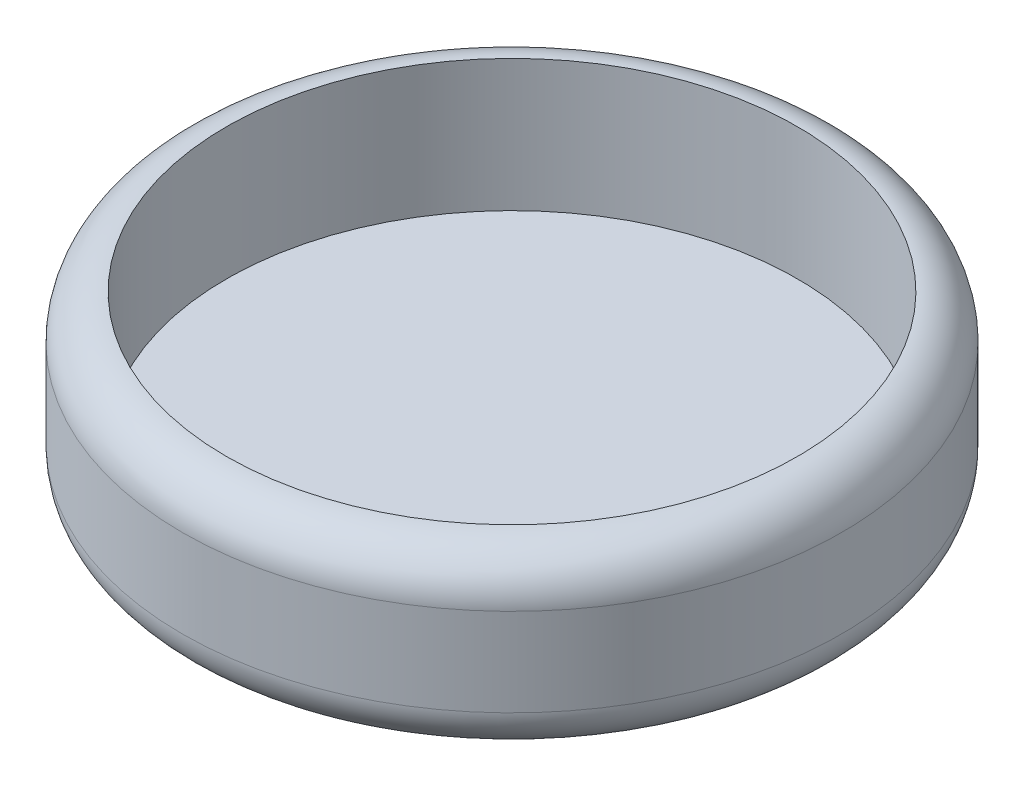
SolidWorks part; units mm, degrees
material "Silicon"
ref_plane "Ön Düzlem" through (0, 0, 0) normal (0, 0, 1) x (1, 0, 0)
ref_plane "Üst Düzlem" through (0, 0, 0) normal (0, 1, 0) x (1, 0, 0)
ref_plane "Sağ Düzlem" through (0, 0, 0) normal (1, 0, 0) x (0, 0, -1)
sketch "Sketch1" plane through (0, 0, 0) normal (0, 1, 0) x (1, 0, 0)
  circle A0 centre (0, 0) radius 7.5
  dimension "D1" = 15
extrude "Boss-Extrude1" add sketch "Sketch1" along normal blind 4
sketch "Sketch2" plane through (0, 4, 0) normal (0, 1, 0) x (1, 0, 0)
  circle A0 centre (0, 0) radius 6.5
  dimension "D1" = 13
extrude "Cut-Extrude1" cut sketch "Sketch2" against normal blind 3
fillet "Fillet1" radius 1 1 edges at (0, 4, 7.5) type face fillet first side face at (0, 4, 6.5) second side face at (0, 4, 7.5)
fillet "Fillet2" radius 1 1 edges at (0, 0, 7.5)
